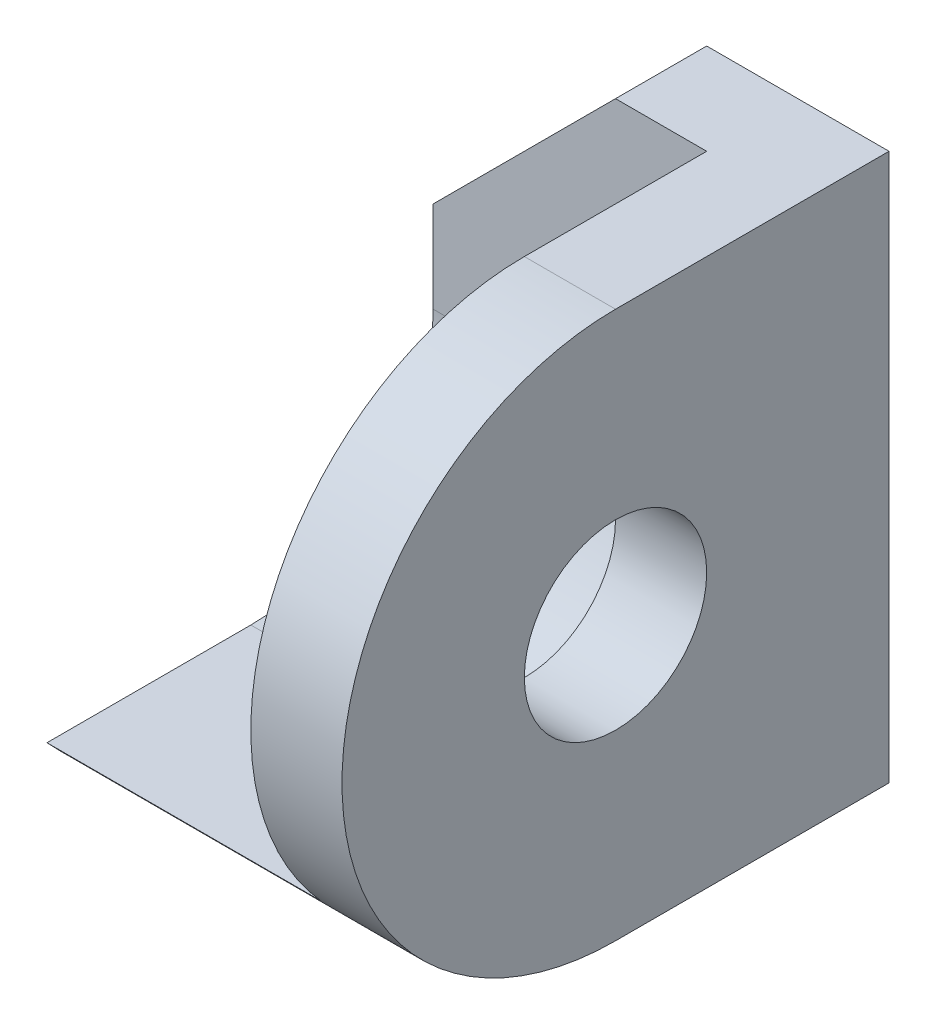
SolidWorks part; units mm, degrees
ref_plane "Front" through (0, 0, 0) normal (0, 0, 1) x (1, 0, 0)
ref_plane "Top" through (0, 0, 0) normal (0, 1, 0) x (1, 0, 0)
ref_plane "Right" through (0, 0, 0) normal (1, 0, 0) x (0, 0, -1)
sketch "Sketch1" plane through (0, 0, 0) normal (1, 0, 0) x (0, 0, -1)
  line L0 (0, 0) -> (0, 6)
  line L1 (0, 6) -> (-3, 6)
  line L2 (0, 0) -> (-3, 0)
  arc A0 (-3, 6) -> (-3, 0) centre (-3, 3) ccw
  circle A1 centre (-3, 3) radius 1
  dimension "D1" = 2
  dimension "D2" = 3
  dimension "D3" = 3
  dimension "D4" = 6
extrude "Boss-Extrude1" add sketch "Sketch1" along normal blind 1 and the other way blind 3
sketch "Sketch2" plane through (-3, 0, 0) normal (-1, 0, 0) x (0, 0, 1)
  line L0 (3, 0) -> (0, 0) construction
  line L1 (0, 0) -> (0, 6) construction
  line L2 (3, 1) -> (7.6141, 1)
  line L3 (7.6141, 1) -> (7.6141, 6.1742)
  line L4 (7.6141, 6.1742) -> (1, 6.1742)
  line L5 (1, 6.1742) -> (1, 4.0204)
  line L6 (1, 4.0204) -> (1, 3)
  arc A0 (3, 1) -> (1, 3) centre (3, 3) cw
  dimension "D5" = 2
  dimension "D1" = 1
  dimension "D2" = 2
  dimension "D3" = 1
  dimension "D4" = 2
extrude "Cut-Extrude2" cut sketch "Sketch2" against normal blind 3
fillet "Chamfer1" radius 2 1 edges at (-3, 6, 0.5) profile chamfer
